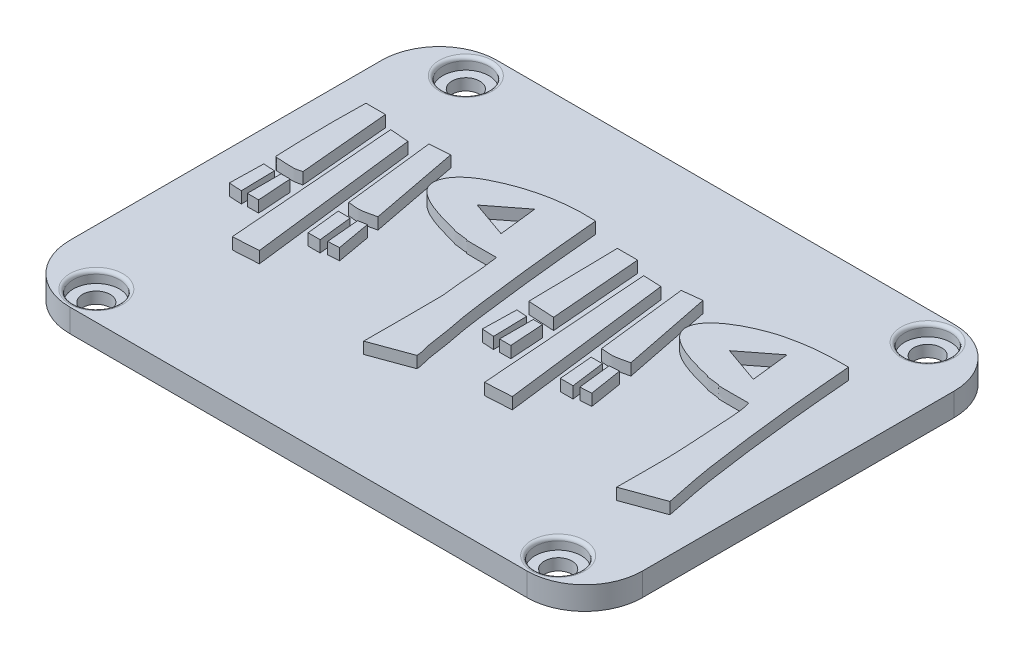
SolidWorks part; units mm, degrees
ref_plane "前视基准面" through (0, 0, 0) normal (0, 0, 1) x (1, 0, 0)
ref_plane "上视基准面" through (0, 0, 0) normal (0, 1, 0) x (1, 0, 0)
ref_plane "右视基准面" through (0, 0, 0) normal (1, 0, 0) x (0, 0, -1)
sketch "草图1" plane through (0, 0, 0) normal (0, 1, 0) x (1, 0, 0)
  line L1 (-24.8, 18.5) -> (24.8, 18.5)
  line L2 (-24.8, 18.5) -> (-24.8, -18.5)
  line L3 (-24.8, -18.5) -> (24.8, -18.5)
  line L4 (24.8, 18.5) -> (24.8, -18.5)
  line L5 (-24.8, 18.5) -> (24.8, -18.5) construction
  line L6 (-24.8, -18.5) -> (24.8, 18.5) construction
  point P0 (0, 0)
  dimension "D1" = 49.6
  dimension "D2" = 37
extrude "凸台-拉伸1" add sketch "草图1" along normal blind 2
fillet "圆角1" radius 5 4 edges at (-24.8, 1, 18.5) (24.8, 1, 18.5) (24.8, 1, -18.5) (-24.8, 1, -18.5)
sketch "草图2" plane through (0, 2, 0) normal (0, 1, 0) x (1, 0, 0)
  line L0 (0, 18.5) -> (0, -18.5) construction
  line L1 (19.8, 18.5) -> (-19.8, 18.5) construction
  line L2 (-19.8, -18.5) -> (19.8, -18.5) construction
  line L3 (-24.8, 0) -> (24.8, 0) construction
  line L4 (-24.8, 13.5) -> (-24.8, -13.5) construction
  line L5 (24.8, -13.5) -> (24.8, 13.5) construction
  circle A0 centre (-20, 16) radius 1.2
  circle A1 centre (-20, -16) radius 1.2
  circle A2 centre (20, -16) radius 1.2
  circle A3 centre (20, 16) radius 1.2
  dimension "D1" = 2.4
  dimension "D2" = 20
  dimension "D3" = 16
extrude "切除-拉伸1" cut sketch "草图2" against normal up to next
sketch "草图3" plane through (0, 2, 0) normal (0, 1, 0) x (1, 0, 0)
  line L0 (0, 18.5) -> (0, -18.5) construction
  line L1 (19.8, 18.5) -> (-19.8, 18.5) construction
  line L2 (-19.8, -18.5) -> (19.8, -18.5) construction
  line L3 (-24.8, 0) -> (24.8, 0) construction
  line L4 (-24.8, 13.5) -> (-24.8, -13.5) construction
  line L5 (24.8, -13.5) -> (24.8, 13.5) construction
  circle A0 centre (-20, 16) radius 2
  circle A1 centre (20, 16) radius 2
  circle A2 centre (20, -16) radius 2
  circle A3 centre (-20, -16) radius 2
  dimension "D1" = 4
extrude "切除-拉伸2" cut sketch "草图3" against normal blind 1
fillet "圆角2" radius 0.3 4 edges at (-20, 2, -14) (20, 2, 18) (20, 2, -18) (-20, 2, 14)
sketch "草图4" plane through (0, 2, 0) normal (0, 1, 0) x (1, 0, 0)
  line L0 (104.0255, 249.5814) -> (591.0903, 249.5814) construction
  line L1 (-161.744, -48.2462) -> (303.5893, -48.2462) construction
  line L2 (92.9791, 169.5232) -> (558.3124, 169.5232) construction
  line L3 (94.2355, 163.8986) -> (559.5689, 163.8986) construction
  line L4 (21.7728, -8.0954) -> (18.3925, -9.3305)
  line L5 (-0.1342, -8.0954) -> (-3.5145, -9.3305)
  line L6 (7.0814, -7.0553) -> (4.8062, -7.1853)
  line L7 (4.8062, -7.1853) -> (3.7011, 7.7011)
  line L8 (3.7011, 7.7011) -> (5.2613, 7.636)
  line L9 (5.2613, 7.636) -> (7.0814, -7.0553)
  line L10 (-14.8256, -7.0553) -> (-17.0358, -7.1853)
  line L11 (-17.0358, -7.1853) -> (-18.2059, 7.7011)
  line L12 (-18.2059, 7.7011) -> (-16.5807, 7.571)
  line L13 (8.9016, -3.61) -> (7.7965, -3.61)
  line L14 (7.7965, -3.61) -> (7.5365, -0.6847)
  line L15 (8.5116, -0.6847) -> (8.9016, -3.61)
  line L16 (-13.0054, -3.61) -> (-14.0455, -3.61)
  line L17 (-14.0455, -3.61) -> (-14.3705, -0.6847)
  line L18 (-14.3705, -0.6847) -> (-13.3304, -0.6847)
  line L19 (-13.3304, -0.6847) -> (-13.0054, -3.61)
  line L20 (9.2916, -3.415) -> (8.9666, -0.5547)
  line L21 (9.8117, -0.4897) -> (10.2667, -3.35)
  line L22 (-12.5504, -3.415) -> (-12.8104, -0.5547)
  line L23 (-12.0953, -0.4247) -> (-11.5753, -3.35)
  line L24 (2.206, -3.285) -> (2.206, -0.3597)
  line L25 (2.9861, -0.3597) -> (3.1811, -3.285)
  line L26 (1.751, -3.35) -> (0.7109, -3.285)
  line L27 (0.7109, -3.285) -> (0.7759, -0.3597)
  line L28 (1.6859, -0.4247) -> (1.751, -3.35)
  line L29 (-19.636, -3.285) -> (-19.636, -0.3597)
  line L30 (-18.8559, -0.3597) -> (-18.6609, -3.285)
  line L31 (-20.091, -3.35) -> (-21.1961, -3.285)
  line L32 (-21.1961, -3.285) -> (-21.1311, -0.3597)
  line L33 (-20.1561, -0.4247) -> (-20.091, -3.35)
  line L34 (7.3415, 0.4204) -> (6.4314, 8.2211)
  line L35 (6.4314, 8.2211) -> (8.1215, 8.4161)
  line L36 (8.1215, 8.4161) -> (9.6817, 0.6154)
  line L37 (-14.5655, 0.4204) -> (-15.4756, 8.2861)
  line L38 (-15.4756, 8.2861) -> (-13.7205, 8.4161)
  line L39 (-13.7205, 8.4161) -> (-12.2253, 0.6154)
  line L40 (2.9211, 0.6804) -> (0.6458, 0.8104)
  line L41 (0.6458, 0.8104) -> (0.5158, 8.6111)
  line L42 (0.5158, 8.6111) -> (2.271, 8.6111)
  line L43 (2.271, 8.6111) -> (2.9211, 0.6804)
  line L44 (-21.2612, 8.6111) -> (-19.571, 8.6111)
  line L45 (-19.571, 8.6111) -> (-18.8559, 0.7454)
  line L46 (-11.5753, -3.35) -> (-12.5504, -3.415)
  line L47 (-12.0953, -0.4247) -> (-12.8104, -0.5547)
  line L48 (-18.6609, -3.285) -> (-19.636, -3.285)
  line L49 (-19.636, -0.3597) -> (-18.8559, -0.3597)
  line L50 (-5.622, 4.6749) -> (-6.0036, 7.9728)
  line L51 (-6.0036, 7.9728) -> (-8.8079, 5.7913)
  line L52 (-8.8079, 5.7913) -> (-5.622, 4.6749)
  line L53 (16.2279, 4.6749) -> (15.8464, 7.9728)
  line L54 (15.8464, 7.9728) -> (13.0421, 5.7913)
  line L55 (13.0421, 5.7913) -> (16.2279, 4.6749)
  line L56 (9.2916, -3.415) -> (10.2667, -3.35)
  line L57 (9.8117, -0.4897) -> (8.9666, -0.5547)
  line L58 (7.5365, -0.6847) -> (8.5116, -0.6847)
  line L59 (3.1811, -3.285) -> (2.206, -3.285)
  line L60 (2.206, -0.3597) -> (2.9861, -0.3597)
  line L61 (-20.1561, -0.4247) -> (-21.1311, -0.3597)
  line L62 (-16.5807, 7.571) -> (-14.8256, -7.0553)
  line L63 (0.7759, -0.3597) -> (1.6859, -0.4247)
  line L64 (0, 18.5) -> (0, -18.5) construction
  line L65 (19.8, 18.5) -> (-19.8, 18.5) construction
  line L66 (-19.8, -18.5) -> (19.8, -18.5) construction
  line L67 (-24.8, 0) -> (24.8, 0) construction
  line L68 (-24.8, 13.5) -> (-24.8, -13.5) construction
  line L69 (24.8, -13.5) -> (24.8, 13.5) construction
  spline S0 degree 3 poles (18.3925, -9.3305) (18.3925, -7.2719) (18.4559, -5.2096) (18.3275, -3.1549) (18.2841, -2.4615) (18.2568, -1.767) (18.1975, -1.0747) (18.1179, -0.1464) (18.1294, 1.7295) (17.8074, 2.6956) knots 0 0 0 0 1 1 1 2 2 2 3 3 3 3
  spline S1 degree 3 poles (17.8074, 2.6956) (16.9407, 2.6956) (16.0737, 2.6745) (15.2072, 2.6956) (15.1765, 2.6963) (15.1724, 2.7556) (15.1422, 2.7606) (14.7763, 2.8216) (14.4029, 2.8296) (14.0371, 2.8906) (14.0068, 2.8957) (14.0018, 2.9482) (13.9721, 2.9556) (12.8735, 3.2303) (9.3359, 3.9711) (9.4217, 5.6859) (9.5106, 7.464) (12.9207, 8.8667) (14.3621, 9.1962) (14.9007, 9.3193) (15.4415, 9.4356) (15.9873, 9.5212) (17.1236, 9.6995) (18.2823, 9.7162) (19.4326, 9.7162) knots 0 0 0 0 1 1 1 2 2 2 3 3 3 4 4 4 5 5 5 6 6 6 7 7 7 8 8 8 8
  spline S2 degree 3 poles (19.4326, 9.7162) (19.8069, 5.0747) (20.299, 0.5133) (20.9927, -4.065) (21.1684, -5.2244) (21.5551, -6.9344) (21.7728, -8.0954) knots 0 0 0 0 1 1 1 2 2 2 2
  spline S3 degree 3 poles (-3.5145, -9.3305) (-3.5145, -7.0986) (-3.4931, -4.8667) (-3.5145, -2.6349) (-3.5189, -2.1812) (-3.6681, -1.1688) (-3.7095, -0.6847) (-3.7746, 0.0737) (-3.7794, 0.8397) (-3.9046, 1.5905) (-3.9655, 1.9564) (-3.9912, 2.3272) (-4.0346, 2.6956) knots 0 0 0 0 1 1 1 2 2 2 3 3 3 4 4 4 4
  spline S4 degree 3 poles (-4.0346, 2.6956) (-4.9013, 2.6956) (-5.7683, 2.6745) (-6.6348, 2.6956) (-6.6655, 2.6963) (-6.6696, 2.7558) (-6.6998, 2.7606) (-7.0875, 2.8218) (-7.4823, 2.8294) (-7.8699, 2.8906) (-7.9002, 2.8954) (-7.9054, 2.9476) (-7.9349, 2.9556) (-9.0743, 3.2664) (-12.3292, 3.9409) (-12.4203, 5.4908) (-12.4862, 6.6099) (-11.2925, 7.5483) (-10.4052, 8.0261) (-8.0049, 9.3185) (-5.1863, 9.8758) (-2.4744, 9.7162) knots 0 0 0 0 1 1 1 2 2 2 3 3 3 4 4 4 5 5 5 6 6 6 7 7 7 7
  spline S5 degree 3 poles (-2.4744, 9.7162) (-2.1015, 5.5518) (-1.6814, 1.549) (-1.1093, -2.5699) (-1.0306, -3.1363) (-0.8247, -4.1355) (-0.7193, -4.7151) (-0.5937, -5.4056) (-0.5198, -6.1048) (-0.3942, -6.7953) (-0.3293, -7.1524) (-0.1342, -7.6845) (-0.1342, -8.0954) knots 0 0 0 0 1 1 1 2 2 2 3 3 3 4 4 4 4
  spline S7 degree 3 poles (9.6817, 0.6154) (9.2483, 0.5287) (8.822, 0.3921) (8.3816, 0.3554) (8.0354, 0.3265) (7.6882, 0.3987) (7.3415, 0.4204) knots 0 0 0 0 1 1 1 2 2 2 2
  spline S8 degree 3 poles (-12.2253, 0.6154) (-12.6587, 0.5287) (-13.085, 0.3921) (-13.5254, 0.3554) (-13.8716, 0.3265) (-14.2188, 0.3987) (-14.5655, 0.4204) knots 0 0 0 0 1 1 1 2 2 2 2
  spline S9 degree 3 poles (-18.8559, 0.7454) (-19.0949, 0.7056) (-19.3287, 0.6154) (-19.571, 0.6154) (-20.0698, 0.6154) (-20.569, 0.639) (-21.0661, 0.6804) (-21.1272, 0.6855) (-21.194, 0.7492) (-21.1961, 0.8104) (-21.2858, 3.4092) (-21.3376, 6.0119) (-21.2612, 8.6111) knots 0 0 0 0 1 1 1 2 2 2 3 3 3 4 4 4 4
  point P89 (0, 0)
extrude "凸台-拉伸2" add sketch "草图4" along normal blind 1
